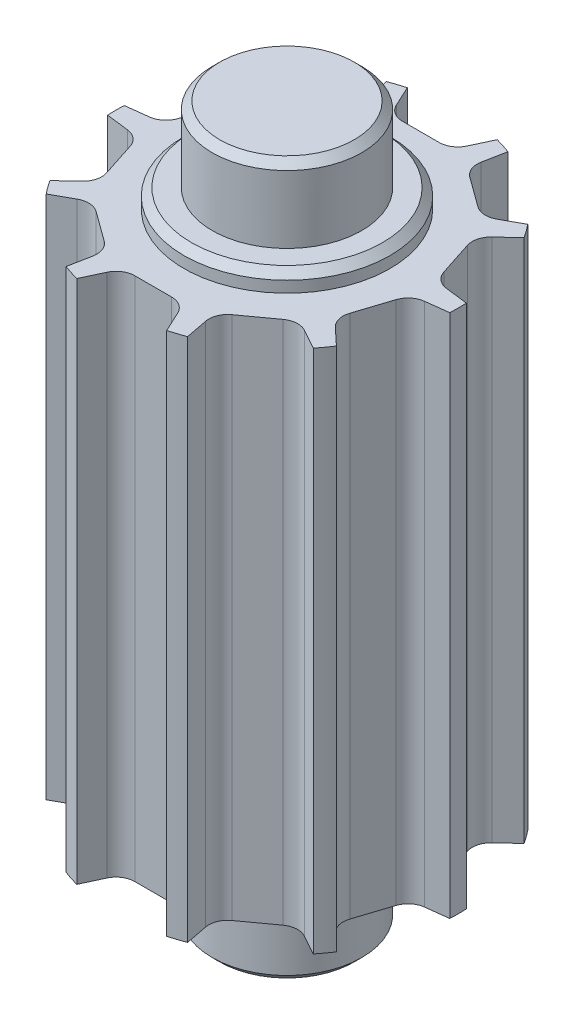
SolidWorks part; units mm, degrees
material "6061-T6 (SS)"
ref_plane "Ebene vorne" through (0, 0, 0) normal (0, 0, 1) x (1, 0, 0)
ref_plane "Ebene oben" through (0, 0, 0) normal (0, 1, 0) x (1, 0, 0)
ref_plane "Ebene rechts" through (0, 0, 0) normal (1, 0, 0) x (0, 0, -1)
ref_axis "Achse1" through (0, -1.8269, 0) along (0, 1, 0)
sketch "Skizze1" plane through (0, 0, 0) normal (0, 1, 0) x (1, 0, 0)
  circle A0 centre (0, 0) radius 4.57
  dimension "D1" = 9.14
extrude "Aufsatz-Linear austragen1" add sketch "Skizze1" along normal blind 19
sketch "Skizze12" plane through (0, 19, 0) normal (0, 1, 0) x (1, 0, 0)
  line L0 (0, 9.2022) -> (0, -8.7185) construction
  line L1 (-8.4713, 0) -> (7.9602, 0) construction
  line L2 (-1.2, 4.4096) -> (-0.8085, 3.57)
  line L3 (1.2, 4.4096) -> (0.8085, 3.57)
  line L4 (-2.6848, 4.57) -> (2.3241, 4.57) construction
  line L5 (-0.8085, 3.57) -> (0.8085, 3.57)
  circle A0 centre (0, 0) radius 3.57 construction
  circle A1 centre (0, 0) radius 4.57 construction
  circle A2 centre (0, 0) radius 4.57 construction
  arc A4 (-1.2, 4.4096) -> (1.2, 4.4096) centre (0, 0) cw
  dimension "D1" = 7.14
  dimension "D6" = 9.14
  dimension "D2" = 2.4
  dimension "D3" = 50
  dimension "D4" = 1.6169
  dimension "D7" = 1
extrude "Schnitt-Linear austragen1" cut sketch "Skizze12" against normal through all
fillet "Verrundung1" radius 0.5 2 edges at (-0.8085, 9.5, -3.57) (0.8085, 9.5, -3.57)
pattern_circular "Kreismuster1" count 10 over 360 about axis through (0, -1.8269, 0) along (0, 1, 0) of "Schnitt-Linear austragen1", "Verrundung1"
sketch "Skizze13" plane through (0, 0, 0) normal (1, 0, 0) x (0, 0, -1)
  line L0 (0, -5.6077) -> (0, 23.9636) construction
  line L1 (-1.995, 0) -> (-10.0768, 0)
  line L2 (-1.995, 0) -> (-1.995, 2)
  line L3 (-1.995, 2) -> (-2.75, 2)
  line L4 (-2.75, 2) -> (-2.75, 2.5)
  line L5 (-2.75, 2.5) -> (-6.4509, 2.5)
  line L6 (-6.4509, 2.5) -> (-6.4509, 16.5)
  line L7 (-6.4509, 16.5) -> (-2.75, 16.5)
  line L8 (-2.75, 16.5) -> (-2.75, 17)
  line L9 (-2.75, 17) -> (-1.995, 17)
  line L10 (-1.995, 17) -> (-1.995, 19)
  line L11 (-10.0768, 0) -> (-10.0768, 19)
  line L12 (-10.0768, 19) -> (-1.995, 19)
  line L14 (0.6372, 19) -> (1.5691, 19) construction
  point P17 (-6.0359, 19)
  dimension "D1" = 3.99
  dimension "D2" = 2
  dimension "D3" = 2
  dimension "D4" = 2.5
  dimension "D5" = 2.5
  dimension "D6" = 5.5
revolve "Schnitt-Rotation1" cut sketch "Skizze13" angle 360 about L0
chamfer "Fase1" distance 0.2 angle 45 4 edges at (0, 0, -1.995) (0, 2, -2.75) (0, 17, -2.75) (0, 19, -1.995)
sketch "Skizze14" plane through (0, 0, 0) normal (1, 0, 0) x (0, 0, -1)
  line L0 (0, -2.8162) -> (0, 4.9138) construction
  line L1 (-4.1884, 0) -> (4.9626, 0) construction
  line L2 (0, 0) -> (-0.6, 0)
  line L3 (-0.6, 0) -> (-0.6, 1.5)
  line L4 (-0.6, 1.5) -> (0, 1.7485)
  line L5 (0, 1.7485) -> (0, 0)
  dimension "D1" = 1.2
  dimension "D2" = 1.5
  dimension "D3" = 67.5
revolve "Schnitt-Rotation2" cut sketch "Skizze14" angle 360 about L0
